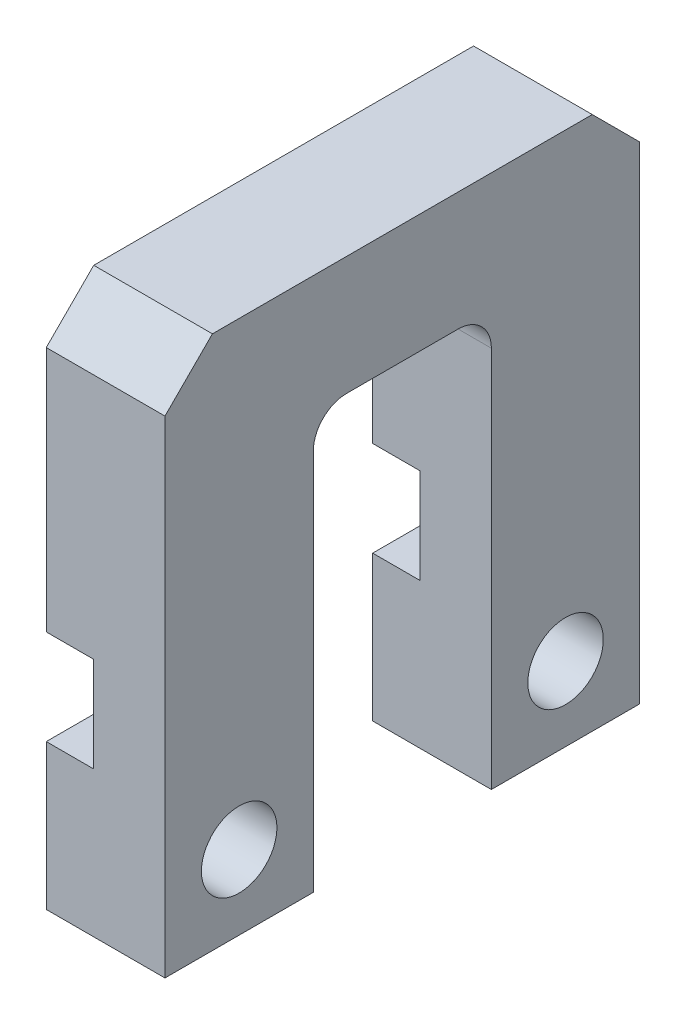
SolidWorks part; units mm, degrees
material "6061-T6 (SS)"
ref_plane "Front" through (0, 0, 0) normal (0, 0, 1) x (1, 0, 0)
ref_plane "Top" through (0, 0, 0) normal (0, 1, 0) x (1, 0, 0)
ref_plane "Right" through (0, 0, 0) normal (1, 0, 0) x (0, 0, -1)
sketch "Sketch1" plane through (0, 0, 0) normal (1, 0, 0) x (0, 0, -1)
  line L0 (7.9375, 0) -> (7.9375, 20.447)
  line L1 (0, 0) -> (7.9375, 0)
  line L2 (0, 0) -> (0, 28.575)
  line L3 (0, 28.575) -> (25.4, 28.575)
  line L4 (25.4, 0) -> (25.4, 28.575)
  line L5 (9.7155, 22.225) -> (15.6845, 22.225)
  line L6 (17.4625, 20.447) -> (17.4625, 0)
  line L7 (17.4625, 0) -> (25.4, 0)
  arc A0 (15.6845, 22.225) -> (17.4625, 20.447) centre (15.6845, 20.447) cw
  arc A1 (7.9375, 20.447) -> (9.7155, 22.225) centre (9.7155, 20.447) cw
  dimension "D5" = 1.778
  dimension "D1" = 28.575
  dimension "D2" = 25.4
  dimension "D3" = 22.225
  dimension "D4" = 9.525
extrude "Boss-Extrude1" add sketch "Sketch1" along normal blind 6.35
sketch "Sketch5" plane through (0, 0, 0) normal (-1, 0, 0) x (0, 0, 1)
  line L0 (-25.4, 0) -> (-21.4312, 3.9688) construction
  line L1 (-21.4312, 3.9688) -> (-17.4625, 0) construction
  line L4 (-7.9375, 0) -> (-3.9688, 3.9688) construction
  line L5 (-3.9688, 3.9688) -> (0, 0) construction
  point P0 (-21.4312, 3.9688)
  point P2 (-3.9688, 3.9688)
hole_wizard "#10-32 Tapped Hole1" positions "Sketch5" profile "Sketch4" tap size "#10-32" standard "ANSI Inch" end condition through all
sketch "Sketch4" plane through (0, 3.9688, -21.4312) normal (0, 1, 0) x (0, 0, 1)
  line L0 (0, 0) -> (0, 6.35)
  line L1 (0, 6.35) -> (2.0193, 6.35)
  line L2 (2.0193, 6.35) -> (2.0193, 0)
  line L5 (2.0193, 0) -> (0, 0)
  line L11 (0, -6.35) -> (0, 107.95) construction
  dimension "Thru Tap Drill Dia." = 4.0386
  dimension "Thru Tap Drill Depth" = 6.35
cosmetic thread "Hole Thread1" parameters "D2"=4.826
cosmetic thread "Hole Thread2" parameters "D2"=4.826
sketch "Sketch2" plane through (0, 0, 0) normal (-1, 0, 0) x (0, 0, 1)
  line L0 (-25.4, 0) -> (-25.4, 28.575) construction
  line L1 (-25.4, 7.7788) -> (0, 7.7788)
  line L2 (-25.4, 7.7788) -> (-25.4, 12.8588)
  line L3 (-25.4, 12.8588) -> (0, 12.8588)
  line L4 (0, 7.7788) -> (0, 12.8588)
  line L5 (0, 28.575) -> (0, 0) construction
  circle A0 centre (-3.9688, 3.9688) radius 2.0193 construction
  point P10 (0, 10.3188)
  dimension "D1" = 5.08
  dimension "D2" = 6.35
extrude "Cut-Extrude1" cut sketch "Sketch2" against normal blind 2.54
chamfer "Chamfer1" distance 2.54 angle 45 2 edges at (3.175, 28.575, -25.4) (3.175, 28.575, 0)
